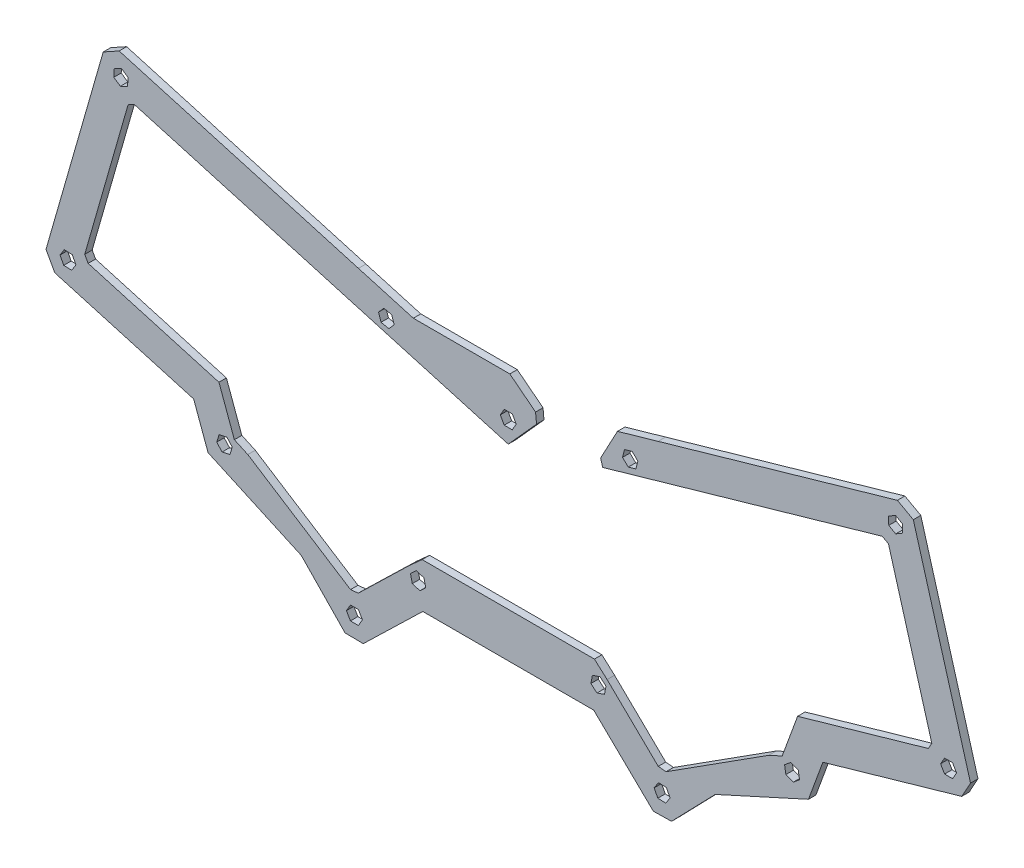
SolidWorks part; units mm, degrees
ref_plane "Plan de face" through (0, 0, 0) normal (0, 0, 1) x (1, 0, 0)
ref_plane "Plan de dessus" through (0, 0, 0) normal (0, 1, 0) x (1, 0, 0)
ref_plane "Plan de droite" through (0, 0, 0) normal (1, 0, 0) x (0, 0, -1)
sketch "Esquisse1" plane through (0, 0, 0) normal (0, 0, 1) x (1, 0, 0)
  line L0 (-121.6461, -32.0475) -> (-108.1875, -28.1884) construction
  line L1 (-108.1875, -28.1884) -> (-104.3283, -41.647) construction
  line L2 (-104.3283, -41.647) -> (-117.7869, -45.5062) construction
  line L3 (-117.7869, -45.5062) -> (-121.6461, -32.0475) construction
  line L4 (-100.1763, -37.9855) -> (-104.0355, -24.5269) construction
  line L5 (-104.0355, -24.5269) -> (-90.5769, -20.6677) construction
  line L6 (-90.5769, -20.6677) -> (-86.7177, -34.1263) construction
  line L7 (-86.7177, -34.1263) -> (-100.1763, -37.9855) construction
  line L8 (-82.5657, -30.4649) -> (-86.4249, -17.0063) construction
  line L9 (-86.4249, -17.0063) -> (-72.9663, -13.1471) construction
  line L10 (-72.9663, -13.1471) -> (-69.1071, -26.6057) construction
  line L11 (-69.1071, -26.6057) -> (-82.5657, -30.4649) construction
  line L12 (-63.6458, -27.5106) -> (-67.505, -14.0519) construction
  line L13 (-67.505, -14.0519) -> (-54.0463, -10.1927) construction
  line L14 (-54.0463, -10.1927) -> (-50.1872, -23.6514) construction
  line L15 (-50.1872, -23.6514) -> (-63.6458, -27.5106) construction
  line L16 (-44.0711, -26.8394) -> (-47.9303, -13.3808) construction
  line L17 (-47.9303, -13.3808) -> (-34.4717, -9.5216) construction
  line L18 (-34.4717, -9.5216) -> (-30.6125, -22.9802) construction
  line L19 (-30.6125, -22.9802) -> (-44.0711, -26.8394) construction
  line L20 (-25.8054, -21.6018) -> (-29.6646, -8.1432) construction
  line L21 (-29.6646, -8.1432) -> (-16.206, -4.284)
  line L22 (-16.206, -4.284) -> (-12.3468, -17.7426)
  line L23 (-12.3468, -17.7426) -> (-25.8054, -21.6018) construction
  line L24 (-116.4086, -50.3128) -> (-102.95, -46.4536) construction
  line L25 (-102.95, -46.4536) -> (-99.0908, -59.9122) construction
  line L26 (-99.0908, -59.9122) -> (-112.5494, -63.7714) construction
  line L27 (-112.5494, -63.7714) -> (-116.4086, -50.3128) construction
  line L28 (-98.798, -42.7922) -> (-85.3394, -38.933) construction
  line L29 (-85.3394, -38.933) -> (-81.4802, -52.3916) construction
  line L30 (-81.4802, -52.3916) -> (-94.9388, -56.2508) construction
  line L31 (-94.9388, -56.2508) -> (-98.798, -42.7922) construction
  line L32 (-81.1874, -35.2715) -> (-67.7288, -31.4123) construction
  line L33 (-67.7288, -31.4123) -> (-63.8696, -44.8709) construction
  line L34 (-63.8696, -44.8709) -> (-77.3282, -48.7301) construction
  line L35 (-77.3282, -48.7301) -> (-81.1874, -35.2715) construction
  line L36 (-62.2675, -32.3172) -> (-48.8089, -28.458) construction
  line L37 (-48.8089, -28.458) -> (-44.9497, -41.9166) construction
  line L38 (-44.9497, -41.9166) -> (-58.4083, -45.7758) construction
  line L39 (-58.4083, -45.7758) -> (-62.2675, -32.3172) construction
  line L40 (-42.6928, -31.646) -> (-29.2342, -27.7869) construction
  line L41 (-29.2342, -27.7869) -> (-25.375, -41.2455) construction
  line L42 (-25.375, -41.2455) -> (-38.8336, -45.1047) construction
  line L43 (-38.8336, -45.1047) -> (-42.6928, -31.646) construction
  line L44 (-24.4271, -26.4084) -> (-10.9685, -22.5492) construction
  line L45 (-10.9685, -22.5492) -> (-7.1093, -36.0078) construction
  line L46 (-7.1093, -36.0078) -> (-20.5679, -39.867) construction
  line L47 (-20.5679, -39.867) -> (-24.4271, -26.4084) construction
  line L48 (-19.1896, -44.6737) -> (-5.731, -40.8145) construction
  line L49 (-5.731, -40.8145) -> (-1.8718, -54.2731) construction
  line L50 (-1.8718, -54.2731) -> (-15.3304, -58.1323) construction
  line L51 (-15.3304, -58.1323) -> (-19.1896, -44.6737) construction
  line L52 (-37.4554, -49.9113) -> (-23.9967, -46.0521) construction
  line L53 (-23.9967, -46.0521) -> (-20.1376, -59.5107) construction
  line L54 (-20.1376, -59.5107) -> (-33.5962, -63.3699) construction
  line L55 (-33.5962, -63.3699) -> (-37.4554, -49.9113) construction
  line L56 (-57.03, -50.5825) -> (-43.5714, -46.7233) construction
  line L57 (-43.5714, -46.7233) -> (-39.7122, -60.1819) construction
  line L58 (-39.7122, -60.1819) -> (-53.1708, -64.0411) construction
  line L59 (-53.1708, -64.0411) -> (-57.03, -50.5825) construction
  line L60 (-75.9499, -53.5368) -> (-62.4913, -49.6776) construction
  line L61 (-62.4913, -49.6776) -> (-58.6321, -63.1362) construction
  line L62 (-58.6321, -63.1362) -> (-72.0908, -66.9954) construction
  line L63 (-72.0908, -66.9954) -> (-75.9499, -53.5368) construction
  line L64 (-93.5605, -61.0574) -> (-80.1019, -57.1982) construction
  line L65 (-80.1019, -57.1982) -> (-76.2427, -70.6569) construction
  line L66 (-76.2427, -70.6569) -> (-89.7013, -74.516) construction
  line L67 (-89.7013, -74.516) -> (-93.5605, -61.0574) construction
  line L68 (-111.1711, -68.5781) -> (-97.7125, -64.7189) construction
  line L69 (-97.7125, -64.7189) -> (-93.8533, -78.1775) construction
  line L70 (-93.8533, -78.1775) -> (-107.3119, -82.0367) construction
  line L71 (-107.3119, -82.0367) -> (-111.1711, -68.5781) construction
  line L72 (-79.0181, -77.3048) -> (-65.5595, -73.4456) construction
  line L73 (-65.5595, -73.4456) -> (-61.7003, -86.9042) construction
  line L74 (-61.7003, -86.9042) -> (-75.1589, -90.7634) construction
  line L75 (-75.1589, -90.7634) -> (-79.0181, -77.3048) construction
  line L76 (-99.4001, -88.1351) -> (-87.3916, -80.9362) construction
  line L77 (-87.3916, -80.9362) -> (-80.1927, -92.9448) construction
  line L78 (-80.1927, -92.9448) -> (-92.2012, -100.1436) construction
  line L79 (-92.2012, -100.1436) -> (-99.4001, -88.1351) construction
  line L80 (-120.0498, -100.4367) -> (-110.317, -90.3719) construction
  line L81 (-110.317, -90.3719) -> (-100.2522, -100.1047) construction
  line L82 (-100.2522, -100.1047) -> (-109.985, -110.1695) construction
  line L83 (-109.985, -110.1695) -> (-120.0498, -100.4367) construction
  line L86 (0.634, -55.7756) -> (-52.9527, -71.1413) construction
  line L89 (-59.2205, -88.2424) -> (-52.9527, -71.1413) construction
  line L96 (-93.4066, -103.0586) -> (-59.4637, -88.3612) construction
  line L97 (-105.418, -115.2057) -> (-93.9754, -103.3509) construction
  line L98 (-126.5332, -96.9919) -> (-107.5003, -115.385) construction
  line L99 (-167.7972, -50.1766) -> (-183.2082, -64.014) construction
  line L100 (-106.3822, -25.4572) -> (-123.6848, -30.4187) construction
  line L101 (-72.1178, -10.6906) -> (-88.4663, -15.3784) construction
  line L102 (-53.2337, -7.6163) -> (-70.5393, -12.5786) construction
  line L103 (-33.6604, -6.9452) -> (-50.9661, -11.9075) construction
  line L104 (-15.3965, -1.7081) -> (-31.745, -6.396) construction
  line L105 (0.5403, -55.2132) -> (-14.6896, -2.0999) construction
  line L106 (-16.199, -60.6113) -> (0.1495, -55.9235) construction
  line L107 (-52.7198, -71.0835) -> (-18.1144, -61.1606) construction
  line L108 (-59.1184, -88.0534) -> (-52.9674, -71.2752) construction
  line L109 (-183.2082, -64.014) -> (-173.1824, -64.9357) construction
  line L113 (-102.2678, -134.438) -> (-84.7238, -116.3191) construction
  line L114 (-84.7238, -116.3191) -> (-47.2969, -99.2981) construction
  line L115 (-47.2969, -99.2981) -> (-41.4917, -83.4594) construction
  line L116 (14.3812, -67.4381) -> (-41.4917, -83.4594) construction
  line L117 (17.8093, -61.2536) -> (-5.1371, 18.7701) construction
  line L122 (-11.3217, 22.1985) -> (-107.4545, -5.3614) construction
  line L129 (-167.7953, -27.6055) -> (-167.7953, -64.7189) construction
  line L130 (-242.0685, -103.8419) -> (-276.37, -88.2424) construction
  line L131 (-229.5108, -116.8112) -> (-242.0685, -103.8419) construction
  line L138 (-208.9328, -96.8551) -> (-229.5108, -116.8112) construction
  line L139 (-225.5107, -79.6567) -> (-208.9328, -96.8551) construction
  line L140 (-109.3352, -134.5492) -> (-102.2678, -134.438) construction
  line L142 (-5.1371, 18.7701) -> (-11.3217, 22.1985) construction
  line L143 (-211.4691, -30.6868) -> (-225.5107, -79.6567) construction
  line L147 (-114.18, -7.2899) -> (-107.4545, -5.3614) construction
  line L148 (-114.18, -7.2899) -> (-123.7936, -10.0465) construction
  line L154 (-4.3102, 15.8863) -> (-127.3606, -19.3904) construction
  line L155 (-131.531, -101.8802) -> (-105.9239, -126.7133) construction
  line L156 (-105.9239, -126.7133) -> (-89.4162, -109.6646) construction
  line L157 (-127.3539, -97.573) -> (-105.9069, -118.3718) construction
  line L158 (-105.9069, -118.3718) -> (-63.5032, -91.2886) construction
  line L159 (-63.5032, -91.2886) -> (-58.4256, -88.9794) construction
  line L160 (-58.4256, -88.9794) -> (-52.1886, -71.9625) construction
  line L161 (1.8709, -56.4612) -> (-52.1886, -71.9625) construction
  line L162 (1.8709, -56.4612) -> (-14.1861, -0.4639) construction
  line L163 (-14.1861, -0.4639) -> (-50.7166, -10.9388) construction
  line L164 (-50.7166, -10.9388) -> (-52.026, -6.3725) construction
  line L165 (-52.026, -6.3725) -> (-70.2913, -11.61) construction
  line L166 (-70.2913, -11.61) -> (-70.911, -9.4488) construction
  line L167 (-70.911, -9.4488) -> (-90.1377, -14.9608) construction
  line L168 (-90.1377, -14.9608) -> (-89.5177, -17.1231) construction
  line L169 (-89.5177, -17.1231) -> (-107.783, -22.3606) construction
  line L170 (-107.783, -22.3606) -> (-107.0938, -24.7639) construction
  line L171 (-107.0938, -24.7639) -> (-125.3583, -30.0011) construction
  line L172 (-125.3583, -30.0011) -> (-111.0411, -79.9324) construction
  line L173 (-110.7998, -78.9627) -> (-127.3777, -96.1611) construction
  line L174 (-89.4162, -109.6646) -> (-53.6562, -93.4017) construction
  line L175 (-53.6562, -93.4017) -> (-47.6042, -76.8897) construction
  line L176 (9.2923, -60.5749) -> (-47.6042, -76.8897) construction
  line L177 (9.2923, -60.5749) -> (-12.0005, 13.6817) construction
  line L178 (-229.7336, -25.4495) -> (-211.4691, -30.6868) construction
  line L179 (-229.0444, -23.0462) -> (-229.7336, -25.4495) construction
  line L180 (-173.1824, -64.9357) -> (-167.7972, -60.1004) construction
  line L181 (-247.3097, -17.8087) -> (-229.0444, -23.0462) construction
  line L185 (17.8093, -61.2536) -> (14.3812, -67.4381) construction
  line L186 (-183.2987, -65.7677) -> (-173.2729, -66.6895) construction
  line L187 (-173.2729, -66.6895) -> (-167.8052, -74.7882) construction
  line L190 (-246.6897, -15.6465) -> (-247.3097, -17.8087) construction
  line L191 (-263.9939, -10.6857) -> (-246.6897, -15.6465) construction
  line L192 (-264.6136, -12.8469) -> (-263.9939, -10.6857) construction
  line L193 (-282.8789, -7.6094) -> (-264.6136, -12.8469) construction
  line L194 (-284.1883, -12.1757) -> (-282.8789, -7.6094) construction
  line L195 (-320.7188, -1.7008) -> (-284.1883, -12.1757) construction
  line L196 (-336.2245, -55.7756) -> (-320.7188, -1.7008) construction
  line L197 (-183.2987, -65.7677) -> (-167.8052, -88.0782) construction
  line L198 (-181.8414, -71.5322) -> (-174.8684, -81.0171) construction
  line L199 (-174.8684, -81.0171) -> (-178.3549, -83.9622) construction
  line L200 (-344.8828, -60.5749) -> (-323.5901, 13.6817) construction
  line L201 (-344.8828, -60.5749) -> (-287.9863, -76.8897) construction
  line L202 (-281.9343, -93.4017) -> (-287.9863, -76.8897) construction
  line L203 (-246.1743, -109.6646) -> (-281.9343, -93.4017) construction
  line L204 (-224.7907, -78.9627) -> (-208.2128, -96.1611) construction
  line L205 (-210.2322, -30.0011) -> (-224.5494, -79.9324) construction
  line L206 (-228.4967, -24.7639) -> (-210.2322, -30.0011) construction
  line L207 (-227.8075, -22.3606) -> (-228.4967, -24.7639) construction
  line L208 (-246.0728, -17.1231) -> (-227.8075, -22.3606) construction
  line L209 (-245.4528, -14.9608) -> (-246.0728, -17.1231) construction
  line L210 (-264.6796, -9.4488) -> (-245.4528, -14.9608) construction
  line L211 (-265.2993, -11.61) -> (-264.6796, -9.4488) construction
  line L212 (-283.5645, -6.3725) -> (-265.2993, -11.61) construction
  line L213 (-284.8739, -10.9388) -> (-283.5645, -6.3725) construction
  line L217 (0.634, -55.7756) -> (-14.8717, -1.7008) construction
  line L220 (-14.8717, -1.7008) -> (-51.4022, -12.1757) construction
  line L221 (-51.4022, -12.1757) -> (-52.7116, -7.6094) construction
  line L222 (-52.7116, -7.6094) -> (-70.9769, -12.8469) construction
  line L223 (-70.9769, -12.8469) -> (-71.5966, -10.6857) construction
  line L224 (-71.5966, -10.6857) -> (-88.9008, -15.6465) construction
  line L225 (-88.9008, -15.6465) -> (-88.2808, -17.8087) construction
  line L226 (-88.2808, -17.8087) -> (-106.5461, -23.0462) construction
  line L227 (-106.5461, -23.0462) -> (-105.8569, -25.4495) construction
  line L228 (-105.8569, -25.4495) -> (-124.1214, -30.6868) construction
  line L231 (-124.1214, -30.6868) -> (-110.0799, -79.6567) construction
  line L232 (-110.0799, -79.6567) -> (-126.6577, -96.8551) construction
  line L233 (-126.6577, -96.8551) -> (-106.0797, -116.8112) construction
  line L234 (-106.0797, -116.8112) -> (-93.522, -103.8419) construction
  line L235 (-93.522, -103.8419) -> (-59.2205, -88.2424) construction
  line L236 (-321.4044, -0.4639) -> (-284.8739, -10.9388) construction
  line L237 (-337.4614, -56.4612) -> (-321.4044, -0.4639) construction
  line L238 (-337.4614, -56.4612) -> (-283.4019, -71.9625) construction
  line L239 (-277.1649, -88.9794) -> (-283.4019, -71.9625) construction
  line L240 (-272.0873, -91.2886) -> (-277.1649, -88.9794) construction
  line L241 (-229.6837, -118.3718) -> (-272.0873, -91.2886) construction
  line L242 (-208.2366, -97.573) -> (-229.6837, -118.3718) construction
  line L243 (-229.6666, -126.7133) -> (-246.1743, -109.6646) construction
  line L244 (-204.0596, -101.8802) -> (-229.6666, -126.7133) construction
  line L245 (-331.2803, 15.8863) -> (-208.2299, -19.3904) construction
  line L246 (-178.3549, -83.9622) -> (-185.8788, -75.0552) construction
  line L247 (-185.8788, -75.0552) -> (-181.8414, -71.5322) construction
  line L248 (-176.7625, -46.6332) -> (-185.5498, -54.5291) construction
  line L249 (-185.5498, -54.5291) -> (-181.1562, -59.4188) construction
  line L250 (-181.1562, -59.4188) -> (-172.3689, -51.5229) construction
  line L251 (-276.4721, -88.0534) -> (-282.6232, -71.2752) construction
  line L252 (-282.8707, -71.0835) -> (-317.4761, -61.1606) construction
  line L253 (-319.3915, -60.6113) -> (-335.74, -55.9235) construction
  line L254 (-336.1309, -55.2132) -> (-320.9009, -2.0999) construction
  line L255 (-320.194, -1.7081) -> (-303.8455, -6.396) construction
  line L256 (-301.9301, -6.9452) -> (-284.6245, -11.9075) construction
  line L257 (-282.3568, -7.6163) -> (-265.0512, -12.5786) construction
  line L258 (-263.4727, -10.6906) -> (-247.1242, -15.3784) construction
  line L259 (-229.2083, -25.4572) -> (-211.9057, -30.4187) construction
  line L260 (-172.3689, -51.5229) -> (-176.7625, -46.6332) construction
  line L261 (-209.0573, -96.9919) -> (-228.0902, -115.385) construction
  line L262 (-230.1725, -115.2057) -> (-241.6151, -103.3509) construction
  line L263 (-242.1839, -103.0586) -> (-276.1268, -88.3612) construction
  line L264 (-276.37, -88.2424) -> (-282.6379, -71.1413) construction
  line L265 (-336.2245, -55.7756) -> (-282.6379, -71.1413) construction
  line L268 (-353.3998, -61.2536) -> (-349.9717, -67.4381) construction
  line L274 (-221.4105, -7.2899) -> (-206.0252, -11.7015) construction
  line L275 (-221.4105, -7.2899) -> (-228.136, -5.3614) construction
  line L276 (-330.4534, 18.7701) -> (-324.2688, 22.1985) construction
  line L277 (-226.2553, -134.5492) -> (-233.3227, -134.438) construction
  line L281 (-324.2688, 22.1985) -> (-228.136, -5.3614) construction
  line L282 (-353.3998, -61.2536) -> (-330.4534, 18.7701) construction
  line L283 (-349.9717, -67.4381) -> (-294.0988, -83.4594) construction
  line L284 (-288.2936, -99.2981) -> (-294.0988, -83.4594) construction
  line L285 (-250.8667, -116.3191) -> (-288.2936, -99.2981) construction
  line L286 (-233.3227, -134.438) -> (-250.8667, -116.3191) construction
  line L288 (-225.6055, -110.1695) -> (-215.5407, -100.4367) construction
  line L289 (-235.3383, -100.1047) -> (-225.6055, -110.1695) construction
  line L290 (-225.2735, -90.3719) -> (-235.3383, -100.1047) construction
  line L291 (-215.5407, -100.4367) -> (-225.2735, -90.3719) construction
  line L292 (-243.3893, -100.1436) -> (-236.1904, -88.1351) construction
  line L293 (-255.3978, -92.9448) -> (-243.3893, -100.1436) construction
  line L294 (-248.1989, -80.9362) -> (-255.3978, -92.9448) construction
  line L295 (-236.1904, -88.1351) -> (-248.1989, -80.9362) construction
  line L296 (-260.4316, -90.7634) -> (-256.5724, -77.3048) construction
  line L297 (-273.8902, -86.9042) -> (-260.4316, -90.7634) construction
  line L298 (-270.031, -73.4456) -> (-273.8902, -86.9042) construction
  line L299 (-256.5724, -77.3048) -> (-270.031, -73.4456) construction
  line L300 (-228.2786, -82.0367) -> (-224.4194, -68.5781) construction
  line L301 (-241.7372, -78.1775) -> (-228.2786, -82.0367) construction
  line L302 (-237.878, -64.7189) -> (-241.7372, -78.1775) construction
  line L303 (-224.4194, -68.5781) -> (-237.878, -64.7189) construction
  line L304 (-245.8892, -74.516) -> (-242.03, -61.0574) construction
  line L305 (-259.3478, -70.6569) -> (-245.8892, -74.516) construction
  line L306 (-255.4886, -57.1982) -> (-259.3478, -70.6569) construction
  line L307 (-242.03, -61.0574) -> (-255.4886, -57.1982) construction
  line L308 (-263.4998, -66.9954) -> (-259.6406, -53.5368) construction
  line L309 (-276.9584, -63.1362) -> (-263.4998, -66.9954) construction
  line L310 (-273.0992, -49.6776) -> (-276.9584, -63.1362) construction
  line L311 (-259.6406, -53.5368) -> (-273.0992, -49.6776)
  line L312 (-282.4197, -64.0411) -> (-278.5605, -50.5825) construction
  line L313 (-295.8783, -60.1819) -> (-282.4197, -64.0411) construction
  line L314 (-292.0191, -46.7233) -> (-295.8783, -60.1819) construction
  line L315 (-278.5605, -50.5825) -> (-292.0191, -46.7233) construction
  line L316 (-301.9944, -63.3699) -> (-298.1352, -49.9113) construction
  line L317 (-315.453, -59.5107) -> (-301.9944, -63.3699) construction
  line L318 (-311.5938, -46.0521) -> (-315.453, -59.5107) construction
  line L319 (-298.1352, -49.9113) -> (-311.5938, -46.0521) construction
  line L320 (-320.2601, -58.1323) -> (-316.4009, -44.6737) construction
  line L321 (-333.7187, -54.2731) -> (-320.2601, -58.1323) construction
  line L322 (-329.8595, -40.8145) -> (-333.7187, -54.2731) construction
  line L323 (-316.4009, -44.6737) -> (-329.8595, -40.8145) construction
  line L324 (-315.0226, -39.867) -> (-311.1634, -26.4084) construction
  line L325 (-328.4812, -36.0078) -> (-315.0226, -39.867) construction
  line L326 (-324.622, -22.5492) -> (-328.4812, -36.0078) construction
  line L327 (-311.1634, -26.4084) -> (-324.622, -22.5492) construction
  line L328 (-296.7569, -45.1047) -> (-292.8977, -31.646) construction
  line L329 (-310.2155, -41.2455) -> (-296.7569, -45.1047) construction
  line L330 (-306.3563, -27.7869) -> (-310.2155, -41.2455) construction
  line L331 (-292.8977, -31.646) -> (-306.3563, -27.7869) construction
  line L332 (-277.1822, -45.7758) -> (-273.323, -32.3172) construction
  line L333 (-290.6408, -41.9166) -> (-277.1822, -45.7758) construction
  line L334 (-286.7817, -28.458) -> (-290.6408, -41.9166) construction
  line L335 (-273.323, -32.3172) -> (-286.7817, -28.458) construction
  line L336 (-258.2623, -48.7301) -> (-254.4031, -35.2715) construction
  line L337 (-271.7209, -44.8709) -> (-258.2623, -48.7301) construction
  line L338 (-267.8617, -31.4123) -> (-271.7209, -44.8709) construction
  line L339 (-254.4031, -35.2715) -> (-267.8617, -31.4123) construction
  line L340 (-240.6517, -56.2508) -> (-236.7925, -42.7922) construction
  line L341 (-254.1103, -52.3916) -> (-240.6517, -56.2508) construction
  line L342 (-250.2511, -38.933) -> (-254.1103, -52.3916) construction
  line L343 (-236.7925, -42.7922) -> (-250.2511, -38.933) construction
  line L344 (-223.0411, -63.7714) -> (-219.1819, -50.3128) construction
  line L345 (-236.4997, -59.9122) -> (-223.0411, -63.7714) construction
  line L346 (-232.6405, -46.4536) -> (-236.4997, -59.9122) construction
  line L347 (-219.1819, -50.3128) -> (-232.6405, -46.4536) construction
  line L348 (-323.2438, -17.7426) -> (-309.7851, -21.6018) construction
  line L349 (-319.3846, -4.284) -> (-323.2438, -17.7426) construction
  line L350 (-305.926, -8.1432) -> (-319.3846, -4.284) construction
  line L351 (-309.7851, -21.6018) -> (-305.926, -8.1432) construction
  line L352 (-304.978, -22.9802) -> (-291.5194, -26.8394) construction
  line L353 (-301.1188, -9.5216) -> (-304.978, -22.9802) construction
  line L354 (-287.6602, -13.3808) -> (-301.1188, -9.5216) construction
  line L355 (-291.5194, -26.8394) -> (-287.6602, -13.3808) construction
  line L356 (-285.4034, -23.6514) -> (-271.9448, -27.5106) construction
  line L357 (-281.5442, -10.1927) -> (-285.4034, -23.6514) construction
  line L358 (-268.0856, -14.0519) -> (-281.5442, -10.1927) construction
  line L359 (-271.9448, -27.5106) -> (-268.0856, -14.0519) construction
  line L360 (-266.4834, -26.6057) -> (-253.0248, -30.4649) construction
  line L361 (-262.6242, -13.1471) -> (-266.4834, -26.6057) construction
  line L362 (-249.1656, -17.0063) -> (-262.6242, -13.1471) construction
  line L363 (-253.0248, -30.4649) -> (-249.1656, -17.0063) construction
  line L364 (-248.8728, -34.1263) -> (-235.4142, -37.9855) construction
  line L365 (-245.0136, -20.6677) -> (-248.8728, -34.1263) construction
  line L366 (-231.555, -24.5269) -> (-245.0136, -20.6677) construction
  line L367 (-235.4142, -37.9855) -> (-231.555, -24.5269) construction
  line L368 (-217.8036, -45.5062) -> (-213.9444, -32.0475) construction
  line L369 (-231.2622, -41.647) -> (-217.8036, -45.5062) construction
  line L370 (-227.4031, -28.1884) -> (-231.2622, -41.647) construction
  line L371 (-213.9444, -32.0475) -> (-227.4031, -28.1884) construction
  line L372 (-226.2553, -134.5492) -> (-202.2968, -111.3509) construction
  line L373 (-109.3352, -134.5492) -> (-133.2937, -111.3509) construction
  line L374 (-141.5559, -103.3509) -> (-194.0347, -103.3509) construction
  line L375 (-167.7972, -50.1766) -> (-152.3861, -64.014) construction
  line L376 (-162.4119, -64.9357) -> (-167.7972, -60.1004) construction
  line L377 (-162.3376, -66.6895) -> (-167.8052, -74.7882) construction
  line L378 (-152.3118, -65.7677) -> (-167.8052, -88.0782) construction
  line L379 (-163.2254, -51.5229) -> (-158.8318, -46.6332) construction
  line L380 (-154.4381, -59.4188) -> (-163.2254, -51.5229) construction
  line L381 (-150.0445, -54.5291) -> (-154.4381, -59.4188) construction
  line L382 (-158.8318, -46.6332) -> (-150.0445, -54.5291) construction
  line L383 (-149.7316, -75.0552) -> (-153.7691, -71.5322) construction
  line L384 (-157.2555, -83.9622) -> (-149.7316, -75.0552) construction
  line L385 (-160.742, -81.0171) -> (-157.2555, -83.9622) construction
  line L386 (-153.7691, -71.5322) -> (-160.742, -81.0171) construction
  line L387 (-152.3118, -65.7677) -> (-162.3376, -66.6895) construction
  line L388 (-152.3861, -64.014) -> (-162.4119, -64.9357) construction
  line L389 (-206.0252, -11.7015) -> (-129.5654, -11.7015) construction
  line L390 (-119.0708, -62.7964) -> (-130.6498, -22.4155) construction
  line L391 (-123.5545, -47.16) -> (-127.4136, -33.7014) construction
  line L392 (-120.442, -65.2702) -> (-138.2688, -70.3819) construction
  line L393 (-140.7426, -69.0107) -> (-154.4194, -21.3141) construction
  line L394 (-167.1758, -11.7015) -> (-206.0252, -11.7015) construction
  line L395 (-156.8153, -19.5087) -> (-167.1758, -11.7015) construction
  line L396 (-123.7936, -10.0465) -> (-130.6498, -22.4155) construction
  line L397 (-138.2688, -70.3819) -> (-140.7426, -69.0107) construction
  line L398 (-119.0708, -62.7964) -> (-120.442, -65.2702) construction
  line L399 (-129.5654, -11.7015) -> (-123.7936, -10.0465) construction
  line L400 (-207.5404, -98.2908) -> (-228.1196, -118.248)
  line L401 (-231.2409, -118.5638) -> (-272.5658, -92.1695)
  line L402 (-272.5658, -92.1695) -> (-277.9598, -89.7165)
  line L403 (-277.9598, -89.7165) -> (-284.166, -72.7837)
  line L404 (-336.7758, -57.6981) -> (-284.166, -72.7837)
  line L405 (-338.147, -55.2243) -> (-320.7131, 5.5749)
  line L406 (-223.5881, -80.208) -> (-202.439, -93.7159) construction
  line L407 (-202.439, -93.7159) -> (-207.5404, -98.2908)
  line L408 (-17.3512, 6.9463) -> (-127.905, -24.7479)
  line L409 (2.5565, -55.2243) -> (-14.8774, 5.5749)
  line L410 (-318.2393, 6.9463) -> (-167.7953, -36.1838)
  line L411 (1.1853, -57.6981) -> (-51.4245, -72.7837)
  line L412 (-57.6307, -89.7165) -> (-51.4245, -72.7837)
  line L413 (-63.0247, -92.1695) -> (-57.6307, -89.7165)
  line L414 (-104.3497, -118.5638) -> (-63.0247, -92.1695)
  line L415 (-207.6856, -24.7479) -> (-223.5881, -80.208) construction
  line L416 (-338.6983, -57.1468) -> (-322.0901, 0.773) construction
  line L417 (-265.3652, -8.212) -> (-244.2159, -14.2752) construction
  line L418 (-208.9953, -29.3155) -> (-223.5881, -80.208) construction
  line L419 (-227.2598, -24.0783) -> (-208.9953, -29.3155) construction
  line L420 (-226.5706, -21.6749) -> (-227.2598, -24.0783) construction
  line L421 (-244.8359, -16.4375) -> (-226.5706, -21.6749) construction
  line L422 (-244.2159, -14.2752) -> (-244.8359, -16.4375) construction
  line L423 (-265.9849, -10.3731) -> (-265.3652, -8.212) construction
  line L424 (-284.2502, -5.1356) -> (-265.9849, -10.3731) construction
  line L425 (-285.5595, -9.7019) -> (-284.2502, -5.1356) construction
  line L426 (-322.0901, 0.773) -> (-285.5595, -9.7019) construction
  line L427 (-128.0501, -98.2908) -> (-107.4709, -118.248)
  line L428 (-133.1515, -93.7159) -> (-128.0501, -98.2908)
  line L429 (-127.905, -24.7479) -> (-167.7953, -36.1862) construction
  line L430 (-129.8233, -25.2979) -> (-130.6498, -22.4155)
  line L431 (-202.439, -93.7159) -> (-133.1515, -93.7159)
  line L432 (-167.7953, -36.1838) -> (-156.4257, -23.5445)
  line L433 (-129.8233, -25.2979) -> (-127.905, -24.7479)
  line L434 (-156.4257, -23.5445) -> (-156.8153, -19.5087)
  line L435 (-320.7131, 5.5749) -> (-318.2393, 6.9463)
  line L436 (-338.6983, -57.1468) -> (-284.166, -72.7837) construction
  line L437 (-338.147, -55.2243) -> (-336.7758, -57.6981)
  line L438 (-207.5404, -98.2908) -> (-229.5553, -119.6404) construction
  line L439 (-229.5553, -119.6404) -> (-272.5658, -92.1695) construction
  line L440 (-228.1196, -118.248) -> (-231.2409, -118.5638)
  line L441 (-107.4709, -118.248) -> (-104.3497, -118.5638)
  line L442 (2.5565, -55.2243) -> (1.1853, -57.6981)
  line L443 (-14.8774, 5.5749) -> (-17.3512, 6.9463)
  line L444 (-133.2937, -111.3509) -> (-202.2968, -111.3509) construction
  line L445 (-214.6968, -14.5277) -> (-217.8401, -13.8763)
  line L446 (-217.8401, -13.8763) -> (-219.9759, -16.2728)
  line L447 (-219.9759, -16.2728) -> (-218.9683, -19.3206)
  line L448 (-218.9683, -19.3206) -> (-215.8251, -19.972)
  line L449 (-215.8251, -19.972) -> (-213.6893, -17.5755)
  line L450 (-213.6893, -17.5755) -> (-214.6968, -14.5277)
  line L451 (-166.1757, -24.834) -> (-169.3858, -24.8172)
  line L452 (-169.3858, -24.8172) -> (-171.0053, -27.5888)
  line L453 (-171.0053, -27.5888) -> (-169.4148, -30.3771)
  line L454 (-169.4148, -30.3771) -> (-166.2047, -30.3939)
  line L455 (-166.2047, -30.3939) -> (-164.5852, -27.6223)
  line L456 (-164.5852, -27.6223) -> (-166.1757, -24.834)
  line L457 (-115.6722, -16.0395) -> (-117.9812, -13.8095)
  line L458 (-117.9812, -13.8095) -> (-121.0669, -14.6941)
  line L459 (-121.0669, -14.6941) -> (-121.8437, -17.8088)
  line L460 (-121.8437, -17.8088) -> (-119.5347, -20.0388)
  line L461 (-119.5347, -20.0388) -> (-116.4489, -19.1542)
  line L462 (-116.4489, -19.1542) -> (-115.6722, -16.0395)
  line L463 (-9.2401, 15.3202) -> (-12.0393, 16.8915)
  line L464 (-12.0393, 16.8915) -> (-14.7996, 15.253)
  line L465 (-14.7996, 15.253) -> (-14.7608, 12.0431)
  line L466 (-14.7608, 12.0431) -> (-11.9616, 10.4718)
  line L467 (-11.9616, 10.4718) -> (-9.2013, 12.1103)
  line L468 (-9.2013, 12.1103) -> (-9.2401, 15.3202)
  line L469 (12.5024, -60.5749) -> (10.8973, -57.7949)
  line L470 (10.8973, -57.7949) -> (7.6873, -57.7949)
  line L471 (7.6873, -57.7949) -> (6.0822, -60.5749)
  line L472 (6.0822, -60.5749) -> (7.6873, -63.3549)
  line L473 (7.6873, -63.3549) -> (10.8973, -63.3549)
  line L474 (10.8973, -63.3549) -> (12.5024, -60.5749)
  line L475 (-50.6498, -94.5269) -> (-51.1786, -91.3606)
  line L476 (-51.1786, -91.3606) -> (-54.185, -90.2355)
  line L477 (-54.185, -90.2355) -> (-56.6626, -92.2765)
  line L478 (-56.6626, -92.2765) -> (-56.1338, -95.4427)
  line L479 (-56.1338, -95.4427) -> (-53.1274, -96.5679)
  line L480 (-53.1274, -96.5679) -> (-50.6498, -94.5269)
  line L481 (-104.4402, -129.5599) -> (-102.7168, -126.8517)
  line L482 (-102.7168, -126.8517) -> (-104.2006, -124.0051)
  line L483 (-104.2006, -124.0051) -> (-107.4076, -123.8667)
  line L484 (-107.4076, -123.8667) -> (-109.131, -126.575)
  line L485 (-109.131, -126.575) -> (-107.6473, -129.4216)
  line L486 (-107.6473, -129.4216) -> (-104.4402, -129.5599)
  line L487 (-132.1348, -105.033) -> (-129.1025, -103.9795)
  line L488 (-129.1025, -103.9795) -> (-128.4987, -100.8268)
  line L489 (-128.4987, -100.8268) -> (-130.9271, -98.7274)
  line L490 (-130.9271, -98.7274) -> (-133.9594, -99.7809)
  line L491 (-133.9594, -99.7809) -> (-134.5633, -102.9336)
  line L492 (-134.5633, -102.9336) -> (-132.1348, -105.033)
  line L493 (-200.9863, -102.8073) -> (-201.7201, -99.6822)
  line L494 (-201.7201, -99.6822) -> (-204.7933, -98.7551)
  line L495 (-204.7933, -98.7551) -> (-207.1328, -100.9531)
  line L496 (-207.1328, -100.9531) -> (-206.3991, -104.0782)
  line L497 (-206.3991, -104.0782) -> (-203.3258, -105.0053)
  line L498 (-203.3258, -105.0053) -> (-200.9863, -102.8073)
  line L499 (-228.0726, -129.4997) -> (-226.4565, -126.726)
  line L500 (-226.4565, -126.726) -> (-228.0506, -123.9397)
  line L501 (-228.0506, -123.9397) -> (-231.2606, -123.927)
  line L502 (-231.2606, -123.927) -> (-232.8766, -126.7006)
  line L503 (-232.8766, -126.7006) -> (-231.2826, -129.4869)
  line L504 (-231.2826, -129.4869) -> (-228.0726, -129.4997)
  line L505 (-279.7615, -95.7646) -> (-278.8016, -92.7014)
  line L506 (-278.8016, -92.7014) -> (-280.9744, -90.3385)
  line L507 (-280.9744, -90.3385) -> (-284.1072, -91.0388)
  line L508 (-284.1072, -91.0388) -> (-285.0671, -94.102)
  line L509 (-285.0671, -94.102) -> (-282.8943, -96.4649)
  line L510 (-282.8943, -96.4649) -> (-279.7615, -95.7646)
  line L511 (-343.3818, -63.4124) -> (-341.6749, -60.6938)
  line L512 (-341.6749, -60.6938) -> (-343.176, -57.8563)
  line L513 (-343.176, -57.8563) -> (-346.3838, -57.7374)
  line L514 (-346.3838, -57.7374) -> (-348.0907, -60.4561)
  line L515 (-348.0907, -60.4561) -> (-346.5896, -63.2936)
  line L516 (-346.5896, -63.2936) -> (-343.3818, -63.4124)
  line L517 (-323.3776, 16.8847) -> (-326.2578, 15.4671)
  line L518 (-326.2578, 15.4671) -> (-326.4702, 12.2641)
  line L519 (-326.4702, 12.2641) -> (-323.8025, 10.4786)
  line L520 (-323.8025, 10.4786) -> (-320.9224, 11.8962)
  line L521 (-320.9224, 11.8962) -> (-320.7099, 15.0992)
  line L522 (-320.7099, 15.0992) -> (-323.3776, 16.8847)
  line L523 (-141.5559, -111.3509) -> (-194.0347, -111.3509) construction
  line L524 (-167.1758, -11.4015) -> (-205.983, -11.4015)
  line L525 (-221.3278, -7.0015) -> (-205.983, -11.4015)
  line L526 (-221.3278, -7.0015) -> (-228.0533, -5.073)
  line L527 (-324.3056, 22.5211) -> (-228.0533, -5.073)
  line L528 (-330.7075, 18.9723) -> (-324.3056, 22.5211)
  line L529 (-353.7224, -61.2904) -> (-330.7075, 18.9723)
  line L530 (-353.7224, -61.2904) -> (-350.1738, -67.6922)
  line L531 (-350.1738, -67.6922) -> (-294.328, -83.7058)
  line L532 (-288.5321, -99.5192) -> (-294.328, -83.7058)
  line L533 (-251.0427, -116.5686) -> (-288.5321, -99.5192)
  line L534 (-233.4517, -134.736) -> (-251.0427, -116.5686)
  line L535 (-226.1358, -134.8511) -> (-233.4517, -134.736)
  line L536 (-226.1358, -134.8511) -> (-202.1754, -111.6509)
  line L537 (-133.4151, -111.6509) -> (-202.1754, -111.6509)
  line L538 (-109.4547, -134.8511) -> (-133.4151, -111.6509)
  line L539 (-109.4547, -134.8511) -> (-102.1388, -134.736)
  line L540 (-102.1388, -134.736) -> (-84.5479, -116.5686)
  line L541 (-84.5479, -116.5686) -> (-47.0584, -99.5192)
  line L542 (-47.0584, -99.5192) -> (-41.2625, -83.7058)
  line L543 (14.5833, -67.6922) -> (-41.2625, -83.7058)
  line L544 (18.1319, -61.2904) -> (14.5833, -67.6922)
  line L545 (18.1319, -61.2904) -> (-4.883, 18.9723)
  line L546 (-4.883, 18.9723) -> (-11.2849, 22.5211)
  line L547 (-11.2849, 22.5211) -> (-107.5372, -5.073)
  line L548 (-114.2627, -7.0015) -> (-107.5372, -5.073)
  line L549 (-114.2627, -7.0015) -> (-123.8763, -9.7581)
  line L550 (-167.1758, -11.4015) -> (-156.8153, -19.5087)
  line L551 (-130.6498, -22.4155) -> (-123.8763, -9.7581)
  circle A2 centre (-12.0005, 13.6817) radius 1.6 construction
  circle A3 centre (-12.0005, 13.6817) radius 3 construction
  circle A4 centre (-118.7579, -16.9241) radius 1.6 construction
  circle A5 centre (9.2923, -60.5749) radius 1.6 construction
  circle A6 centre (-53.6562, -93.4017) radius 1.6 construction
  circle A7 centre (-105.9239, -126.7133) radius 1.6 construction
  circle A8 centre (-131.531, -101.8802) radius 1.6 construction
  circle A10 centre (-147.4897, -45.973) radius 1.6 construction
  circle A11 centre (-323.5901, 13.6817) radius 3 construction
  circle A12 centre (-188.1008, -45.973) radius 1.6 construction
  circle A14 centre (-204.0596, -101.8802) radius 1.6 construction
  circle A15 centre (-229.6666, -126.7133) radius 1.6 construction
  circle A16 centre (-281.9343, -93.4017) radius 1.6 construction
  circle A17 centre (-344.8828, -60.5749) radius 1.6 construction
  circle A18 centre (-216.8326, -16.9241) radius 1.6 construction
  circle A19 centre (-323.5901, 13.6817) radius 1.6 construction
  circle A20 centre (-167.7953, -27.6055) radius 1.6 construction
  circle A21 centre (-216.8326, -16.9241) radius 2.78 construction
  circle A22 centre (-167.7953, -27.6055) radius 2.78 construction
  circle A23 centre (-118.7579, -16.9241) radius 2.78 construction
  circle A24 centre (-12.0005, 13.6817) radius 2.78 construction
  circle A25 centre (9.2923, -60.5749) radius 2.78 construction
  circle A26 centre (-53.6562, -93.4017) radius 2.78 construction
  circle A27 centre (-105.9239, -126.7133) radius 2.78 construction
  circle A28 centre (-131.531, -101.8802) radius 2.78 construction
  circle A29 centre (-204.0596, -101.8802) radius 2.78 construction
  circle A30 centre (-229.6666, -126.7133) radius 2.78 construction
  circle A31 centre (-281.9343, -93.4017) radius 2.78 construction
  circle A32 centre (-344.8828, -60.5749) radius 2.78 construction
  circle A33 centre (-323.5901, 13.6817) radius 2.78 construction
  point P138 (-167.7953, -27.6055)
  point P139 (-6.5153, 23.5764)
  point P150 (-169.1046, -23.0392)
  point P200 (19.1875, -66.0599)
  point P203 (-141.5228, -71.3355)
  point P204 (-141.5228, 1.5705)
  point P263 (-133.4062, -12.8029)
  point P264 (-118.5195, -64.7189)
  point P283 (-140.1914, -70.9332)
  point P284 (-157.1758, -11.7015)
  point P405 (-354.778, -66.0599)
  point P406 (-329.0752, 23.5764)
  point P423 (-15.4286, 7.4974)
  point P424 (-320.1619, 7.4974)
  point P429 (3.1078, -57.1468)
  point P434 (-106.0352, -119.6404)
  dimension "D3" = 3.2
  dimension "D4" = 6
  dimension "D6" = 3.2
  dimension "D7" = 3.2
  dimension "D8" = 3.2
  dimension "D9" = 3.2
  dimension "D10" = 3.2
  dimension "D16" = 3.2
  dimension "D21" = 5.56
  dimension "D34" = 5.56
  dimension "D2" = 6
  dimension "D5" = 1
  dimension "D11" = 5.56
  dimension "D14" = 5.56
  dimension "D22" = 5.56
  dimension "D26" = 5.56
  dimension "D27" = 5.56
  dimension "D28" = 5.56
  dimension "D29" = 5.56
  dimension "D30" = 5.56
  dimension "D31" = 5.56
  dimension "D32" = 5.56
  dimension "D33" = 5.56
  dimension "D35" = 8
  dimension "D36" = 0.3
extrude "Boss.-Extru.1" add sketch "Esquisse1" along normal blind 3 contours L443 L409 L442 L411 L412 L413 L414 L441 L427 L428 L431 L407 L400 L440 L401 L402 L403 L404 L437 L405 L435 L410 L432 L434 L395 L394 L274 L275 L281 L276 L282 L268 L283 L284 L285 L286 L277 L372 L374 L373 L140 L113 L114 L115 L116 L185 L117 L142 L122 L147 L148 region at (-202.2939, -99.0095, 0)
